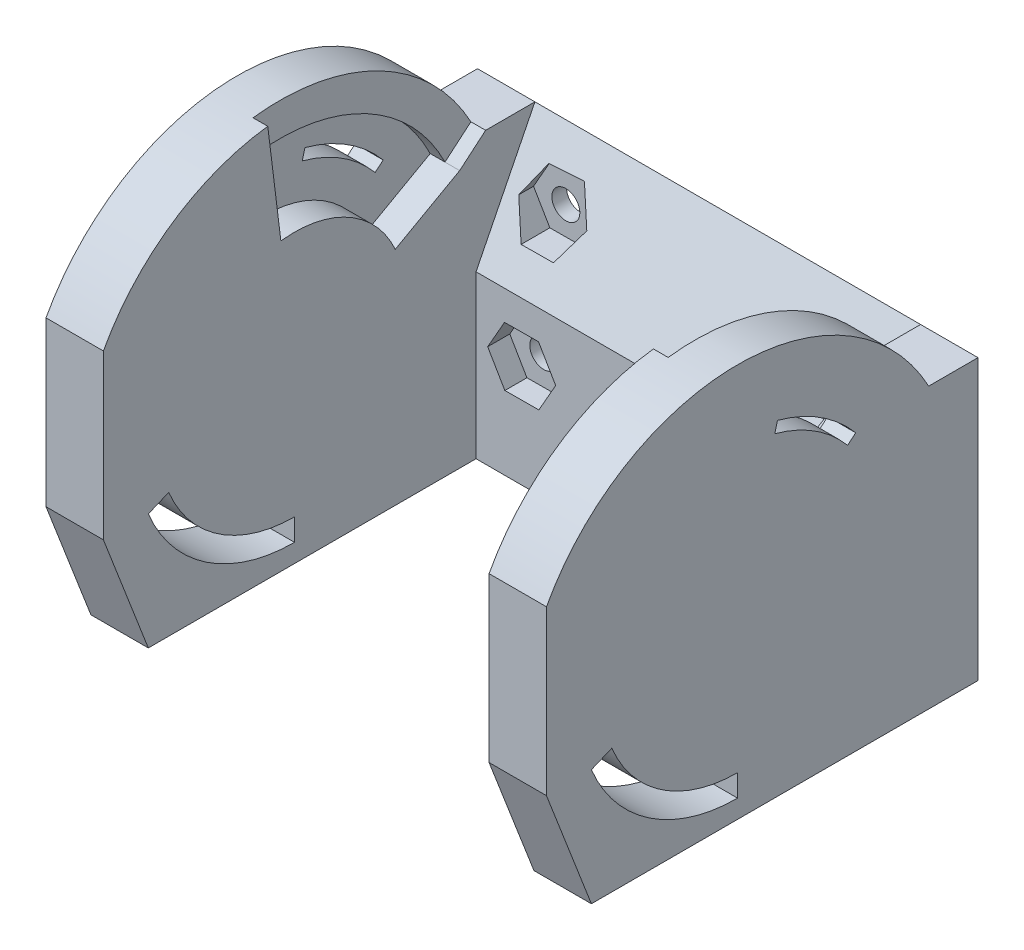
SolidWorks part; units mm, degrees
ref_plane "Alzado" through (0, 0, 0) normal (0, 0, 1) x (1, 0, 0)
ref_plane "Planta" through (0, 0, 0) normal (0, 1, 0) x (1, 0, 0)
ref_plane "Vista lateral" through (0, 0, 0) normal (1, 0, 0) x (0, 0, -1)
sketch "Croquis1" plane through (0, 0, 0) normal (0, 0, 1) x (1, 0, 0)
  line L1 (-48.8873, 14.6225) -> (-14.8873, 14.6225)
  line L2 (-48.8873, 14.6225) -> (-48.8873, -4.3775)
  line L3 (-48.8873, -4.3775) -> (-14.8873, -4.3775)
  line L4 (-14.8873, 14.6225) -> (-14.8873, -4.3775)
  dimension "D1" = 19
  dimension "D2" = 34
extrude "Saliente-Extruir1" add sketch "Croquis1" along normal blind 35
sketch "Croquis2" plane through (0, -4.3775, 0) normal (0, -1, 0) x (1, 0, 0)
  line L0 (-48.8873, 35) -> (-14.8873, 35) construction
  line L1 (-44.9873, 35) -> (-18.7873, 35)
  line L2 (-44.9873, 35) -> (-44.9873, 4)
  line L3 (-44.9873, 4) -> (-18.7873, 4)
  line L4 (-18.7873, 35) -> (-18.7873, 4)
  line L5 (-48.8873, 35) -> (-48.8873, 0) construction
  line L6 (-14.8873, 35) -> (-14.8873, 0) construction
  line L7 (-48.8873, 0) -> (-14.8873, 0) construction
  dimension "D1" = 3.9
  dimension "D2" = 3.9
  dimension "D3" = 26.2
  dimension "D4" = 4
extrude "Cortar-Extruir1" cut sketch "Croquis2" against normal blind 25
sketch "Croquis4" plane through (-18.7873, 0, 0) normal (-1, 0, 0) x (0, 0, 1)
  line L0 (4, 14.6225) -> (4, 6.6225)
  line L1 (4, 14.6225) -> (4, -4.3775) construction
  line L2 (4, 6.6225) -> (0, 14.6225)
  line L3 (0, 14.6225) -> (4, 14.6225)
extrude "Cortar-Extruir3" cut sketch "Croquis4" along normal up to vertex (26.2 mm away) up to point (-44.9873, 14.6225, 4)
sketch "Croquis9" plane through (-14.8873, 0, 0) normal (1, 0, 0) x (0, 0, -1)
  line L0 (-35, 14.6225) -> (0, 14.6225) construction
  line L1 (-29.3158, 14.6225) -> (-3.3495, 14.6225)
  line L7 (-35, -4.3775) -> (0, -4.3775) construction
  arc A0 (-29.3158, 14.6225) -> (-3.3495, 14.6225) centre (-16.3327, 7.6225) cw
  dimension "D2" = 12
extrude "Saliente-Extruir2" add sketch "Croquis9" against normal up to vertex (34 mm away) up to point (-48.8873, 14.6225, 35)
sketch "Croquis10" plane through (0, 14.6225, 0) normal (0, -1, 0) x (1, 0, 0)
  line L1 (-44.9873, 29.3158) -> (-18.7873, 29.3158)
  line L2 (-44.9873, 29.3158) -> (-44.9873, 3.3495)
  line L3 (-44.9873, 3.3495) -> (-18.7873, 3.3495)
  line L4 (-18.7873, 29.3158) -> (-18.7873, 3.3495)
extrude "Cortar-Extruir4" cut sketch "Croquis10" against normal blind 10
sketch "Croquis11" plane through (-14.8873, 0, 0) normal (1, 0, 0) x (0, 0, -1)
  line L0 (-26.2646, 3.5092) -> (-24.8787, 4.0831)
  line L1 (-16.3327, -1.6275) -> (-16.3327, -3.1275)
  line L3 (-13.6215, 17.7406) -> (-13.8072, 17.0476)
  line L4 (-8.3084, 14.3557) -> (-8.858, 13.8945)
  arc A2 (-8.3084, 14.3557) -> (-13.6215, 17.7406) centre (-16.3327, 7.6225) ccw
  arc A3 (-24.8787, 4.0831) -> (-16.3327, -1.6275) centre (-16.3327, 7.6225) ccw
  arc A4 (-13.8072, 17.0476) -> (-8.858, 13.8945) centre (-16.3327, 7.6225) cw
  arc A5 (-26.2646, 3.5092) -> (-16.3327, -3.1275) centre (-16.3327, 7.6225) ccw
extrude "Cortar-Extruir5" cut sketch "Croquis11" against normal up to vertex (34 mm away) up to point (-48.8873, 14.6225, 3.3495)
sketch "Croquis12" plane through (-18.7873, 0, 0) normal (-1, 0, 0) x (0, 0, 1)
  line L0 (17.2589, 15.0651) -> (17.8732, 20.0273)
  line L1 (5.1129, 13.1331) -> (9.4881, 10.6887)
  arc A2 (9.4881, 10.6887) -> (17.2589, 15.0651) centre (16.3327, 7.6225) cw
  arc A3 (5.1129, 13.1331) -> (17.8732, 20.0273) centre (16.3327, 7.6225) cw
extrude "Cortar-Extruir6" cut sketch "Croquis12" against normal blind 2
sketch "Croquis14" plane through (-18.7873, 0, 0) normal (-1, 0, 0) x (0, 0, 1)
  line L0 (5.1129, 13.1331) -> (9.4881, 10.6887) construction
  line L1 (17.8732, 20.0273) -> (17.2589, 15.0651)
  line L2 (9.4881, 10.6887) -> (5.1129, 13.1331)
  arc A0 (17.2589, 15.0651) -> (9.4881, 10.6887) centre (16.3327, 7.6225) ccw
  arc A1 (17.2589, 15.0651) -> (9.4881, 10.6887) centre (16.3327, 7.6225) ccw construction
  arc A2 (17.8732, 20.0273) -> (5.1129, 13.1331) centre (16.3327, 7.6225) ccw
extrude "Cortar-Extruir7" cut sketch "Croquis14" along normal blind 28.2
sketch "Croquis15" plane through (-18.7873, 0, 0) normal (-1, 0, 0) x (0, 0, 1)
  line L0 (17.8732, 20.0273) -> (18.1505, 22.2601)
  line L1 (3.3495, 14.6225) -> (5.1129, 13.1331)
  arc A0 (17.8732, 20.0273) -> (5.1129, 13.1331) centre (16.3327, 7.6225) ccw
  arc A1 (17.8732, 20.0273) -> (5.1129, 13.1331) centre (16.3327, 7.6225) ccw construction
  arc A2 (29.3158, 14.6225) -> (3.3495, 14.6225) centre (16.3327, 7.6225) ccw construction
  arc A3 (18.1505, 22.2601) -> (3.3495, 14.6225) centre (16.3327, 7.6225) ccw
extrude "Cortar-Extruir8" cut sketch "Croquis15" against normal blind 1
extrude "Cortar-Extruir9" cut sketch "Croquis15<2>" along normal blind 27.2
sketch "Croquis15<2>" plane through (-18.7873, 0, 0) normal (-1, 0, 0) x (0, 0, 1) same geometry as "Croquis15"
sketch "Croquis17" plane through (-14.8873, 0, 0) normal (1, 0, 0) x (0, 0, -1)
  line L0 (-29.3158, 3.5092) -> (-29.3158, 14.6225)
  line L1 (-29.3158, 14.6225) -> (-35, 14.6225)
  line L2 (-35, 14.6225) -> (-35, -4.3775)
  line L3 (-35, -4.3775) -> (-26.2646, -4.3775)
  line L4 (-35, -4.3775) -> (0, -4.3775) construction
  line L5 (-26.2646, -4.3775) -> (-29.3158, 3.5092)
extrude "Cortar-Extruir10" cut sketch "Croquis17" against normal up to vertex (34 mm away) up to point (-48.8873, -4.3775, 35)
sketch "Croquis18" plane through (0, 0, 0) normal (0, 0, -1) x (-1, 0, 0)
  line L0 (48.8873, -4.3775) -> (14.8873, -4.3775) construction
  line L2 (48.8873, 14.6225) -> (48.8873, -4.3775) construction
  circle A0 centre (41.8873, 2.6225) radius 0.95
  circle A1 centre (21.8873, 2.6225) radius 0.95
  circle A2 centre (21.8873, 10.6225) radius 0.95
  circle A3 centre (41.8873, 10.6225) radius 0.95
  dimension "D1" = 7
  dimension "D2" = 7
  dimension "D3" = 2
  dimension "D4" = 2
extrude "Cortar-Extruir11" cut sketch "Croquis18" against normal up to vertex (4 mm away) up to point (-18.7873, -4.3775, 4)
sketch "Croquis19" plane through (0, 0, 4) normal (0, 0, 1) x (1, 0, 0)
  line L0 (-43.0308, 0.6161) -> (-40.7214, 0.629)
  line L1 (-23.0308, 0.6161) -> (-20.7214, 0.629)
  line L2 (-20.7214, 0.629) -> (-19.5779, 2.6355)
  line L3 (-19.5779, 2.6355) -> (-20.7438, 4.629)
  line L4 (-20.7438, 4.629) -> (-23.0531, 4.6161)
  line L5 (-23.0531, 4.6161) -> (-24.1966, 2.6096)
  line L6 (-24.1966, 2.6096) -> (-23.0308, 0.6161)
  line L7 (-40.7214, 0.629) -> (-39.5779, 2.6355)
  line L8 (-39.5779, 2.6355) -> (-40.7438, 4.629)
  line L9 (-40.7438, 4.629) -> (-43.0531, 4.6161)
  line L10 (-43.0531, 4.6161) -> (-44.1966, 2.6096)
  line L11 (-44.1966, 2.6096) -> (-43.0308, 0.6161)
  circle A0 centre (-21.8873, 2.6225) radius 2 construction
  circle A1 centre (-41.8873, 2.6225) radius 2 construction
  dimension "D1" = 4
  dimension "D2" = 2
extrude "Cortar-Extruir12" cut sketch "Croquis19" against normal blind 1.5
sketch "Croquis20" plane through (0, 0, 4) normal (0, 0, 1) x (1, 0, 0)
  line L12 (-44.0812, 10.6103) -> (-42.9736, 8.7165)
  line L13 (-42.9736, 8.7165) -> (-40.7797, 8.7287)
  line L14 (-40.7797, 8.7287) -> (-39.5207, 10.7358)
  line L15 (-39.5207, 10.7358) -> (-40.6283, 12.6296)
  line L16 (-40.6283, 12.6296) -> (-42.9948, 12.5164)
  line L17 (-42.9948, 12.5164) -> (-44.0812, 10.6103)
  line L18 (-24.0812, 10.6103) -> (-22.9736, 8.7165)
  line L19 (-22.9736, 8.7165) -> (-20.7797, 8.7287)
  line L20 (-20.7797, 8.7287) -> (-19.5207, 10.7358)
  line L21 (-19.5207, 10.7358) -> (-20.6283, 12.6296)
  line L22 (-20.6283, 12.6296) -> (-22.9948, 12.5164)
  line L23 (-22.9948, 12.5164) -> (-24.0812, 10.6103)
  circle A2 centre (-41.8873, 10.6225) radius 1.9 construction
  circle A3 centre (-21.8873, 10.6225) radius 1.9 construction
  dimension "D1" = 4
  dimension "D2" = 4
extrude "Cortar-Extruir13" cut sketch "Croquis20" against normal blind 3
